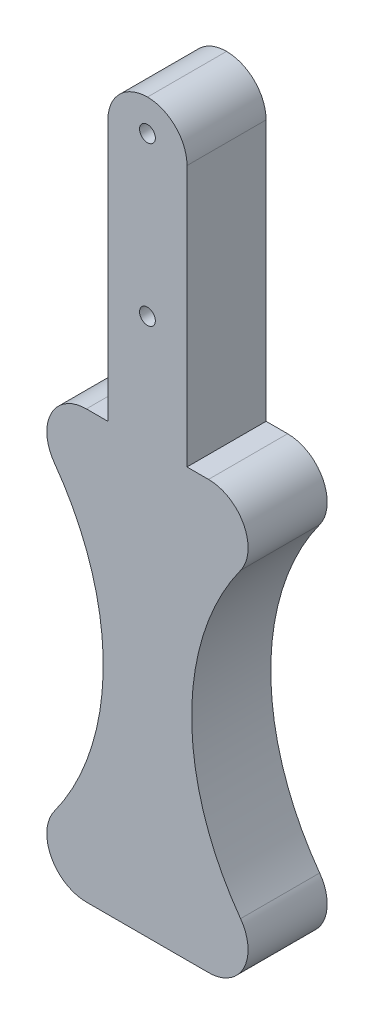
SolidWorks part; units mm, degrees
ref_plane "Front" through (0, 0, 0) normal (0, 0, 1) x (1, 0, 0)
ref_plane "Top" through (0, 0, 0) normal (0, 1, 0) x (1, 0, 0)
ref_plane "Right" through (0, 0, 0) normal (1, 0, 0) x (0, 0, -1)
sketch "Esquisse1" plane through (0, 0, 0) normal (0, 0, 1) x (1, 0, 0)
  line L1 (0, 0) -> (10, 0)
  line L2 (0, 0) -> (0, 92)
  line L3 (0, 92) -> (10, 92)
  line L4 (10, 0) -> (10, 92)
  dimension "D1" = 10
  dimension "D2" = 92
extrude "Boss.-Extru.1" add sketch "Esquisse1" along normal blind 10
sketch "Esquisse2" plane through (0, 0, 10) normal (0, 0, 1) x (1, 0, 0)
  line L0 (5, 92) -> (5, 68) construction
  line L1 (10, 92) -> (0, 92) construction
  circle A0 centre (5, 68) radius 1
  circle A1 centre (5, 88) radius 1
  dimension "D1" = 20
  dimension "D2" = 4
  dimension "D3" = 2
extrude "Enlèv. mat.-Extru.1" cut sketch "Esquisse2" against normal up to vertex (10 mm away) up to point (0, 92, 0)
fillet "Congé1" radius 5 2 edges at (10, 92, 5) (0, 92, 5)
sketch "Esquisse3" plane through (0, 0, 10) normal (0, 0, 1) x (1, 0, 0)
  line L0 (0, 0) -> (0, 54)
  line L1 (0, 87) -> (0, 0) construction
  line L2 (0, 54) -> (-15, 54)
  line L3 (-15, 0) -> (0, 0)
  line L4 (-15, 54) -> (-15, 0) construction
  line L5 (5, 0) -> (5, 34.4675) construction
  line L6 (0, 0) -> (10, 0) construction
  line L7 (25, 54) -> (25, 0) construction
  line L8 (25, 0) -> (10, 0)
  line L9 (10, 54) -> (25, 54)
  line L10 (10, 0) -> (10, 54)
  arc A0 (-15, 54) -> (-15, 0) centre (-33.0901, 27) cw
  arc A1 (25, 54) -> (25, 0) centre (43.0901, 27) ccw
  dimension "D1" = 32.5
  dimension "D2" = 15
  dimension "D3" = 54
extrude "Boss.-Extru.2" add sketch "Esquisse3" against normal up to vertex (10 mm away) up to point (10, 0, 0)
fillet "Congé2" radius 5 4 edges at (25, 0, 5) (25, 54, 5) (-15, 54, 5) (-15, 0, 5)
